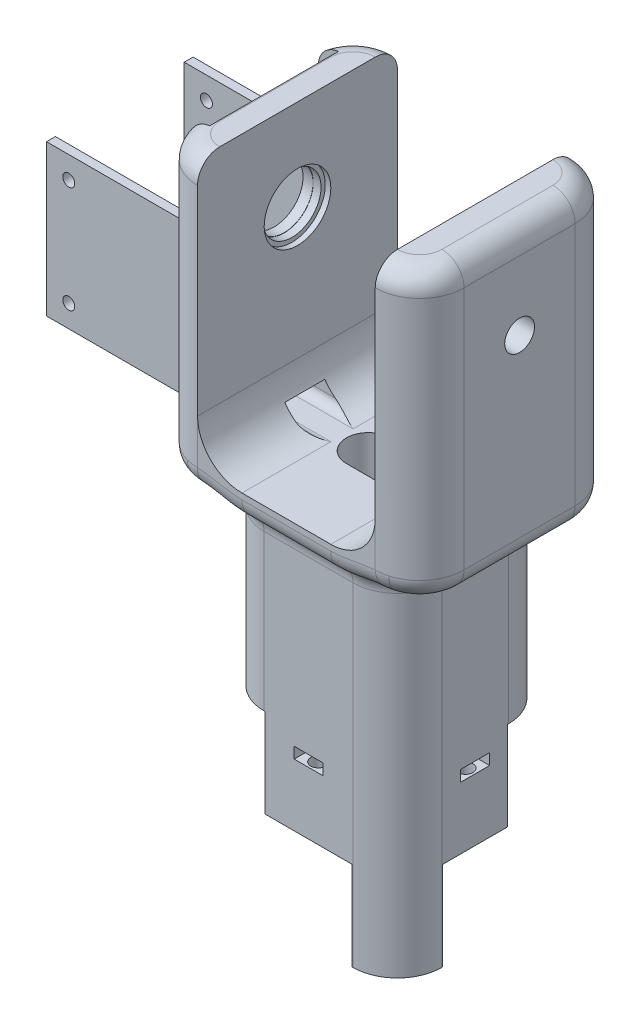
SolidWorks part; units mm, degrees
ref_plane "Plan de face" through (0, 0, 0) normal (0, 0, 1) x (1, 0, 0)
ref_plane "Plan de dessus" through (0, 0, 0) normal (0, 1, 0) x (1, 0, 0)
ref_plane "Plan de droite" through (0, 0, 0) normal (1, 0, 0) x (0, 0, -1)
sketch "Esquisse1" plane through (0, 0, 0) normal (0, 1, 0) x (1, 0, 0)
  line L1 (-20, -17.5) -> (20, -17.5)
  line L2 (-20, -17.5) -> (-20, 17.5)
  line L3 (-20, 17.5) -> (20, 17.5)
  line L4 (20, -17.5) -> (20, 17.5)
  line L5 (-20, -17.5) -> (20, 17.5) construction
  line L6 (-20, 17.5) -> (20, -17.5) construction
  point P0 (0, 0)
  dimension "D1" = 40
  dimension "D2" = 35
extrude "Boss.-Extru.1" add sketch "Esquisse1" along normal blind 80
fillet "Congé1" radius 10 4 edges at (-20, 40, 17.5) (-20, 40, -17.5) (20, 40, -17.5) (20, 40, 17.5)
sketch "Esquisse4" plane through (0, 0, 0) normal (0, -1, 0) x (1, 0, 0)
  line L10 (-20, 17.5) -> (9.8, 17.5)
  line L11 (9.8, 17.5) -> (9.8, 7.3)
  line L12 (9.8, 7.3) -> (20, 7.3)
  line L13 (20, 7.5) -> (20, -7.5) construction
  line L14 (20, 7.3) -> (20, -17.5)
  line L15 (20, -17.5) -> (-9.8, -17.5)
  line L16 (-9.8, -17.5) -> (-9.8, -7.3)
  line L17 (-9.8, -7.3) -> (-20, -7.3)
  line L18 (-20, -7.5) -> (-20, 7.5) construction
  line L19 (-20, -7.3) -> (-20, 17.5)
  line L20 (-10, 17.5) -> (10, 17.5) construction
  line L21 (10, -17.5) -> (-10, -17.5) construction
  arc A2 (-20, -7.5) -> (-10, -17.5) centre (-10, -7.5) ccw construction
  arc A3 (20, 7.5) -> (10, 17.5) centre (10, 7.5) ccw construction
  dimension "D1" = 0.2
  dimension "D2" = 0.2
  dimension "D3" = 0.2
  dimension "D4" = 0.2
extrude "Enlèv. mat.-Extru.3" cut sketch "Esquisse4" against normal blind 20
sketch "Esquisse5" plane through (0, 20, 0) normal (0, -1, 0) x (1, 0, 0)
  line L0 (-20, 7.5) -> (-20, -7.3) construction
  line L9 (-9.8, 7.3) -> (-20, 7.3)
  line L10 (-9.8, 7.3) -> (-9.8, 17.5)
  line L11 (-9.8, 17.5) -> (-20, 17.5)
  line L12 (-20, 7.3) -> (-20, 17.5)
  line L13 (20, -17.5) -> (9.8, -17.5)
  line L14 (20, -17.5) -> (20, -7.3)
  line L15 (20, -7.3) -> (9.8, -7.3)
  line L16 (9.8, -17.5) -> (9.8, -7.3)
  line L17 (9.8, 17.5) -> (-10, 17.5) construction
  line L18 (20, -7.5) -> (20, 7.3) construction
  line L19 (-9.8, -17.5) -> (10, -17.5) construction
  arc A0 (-10, 17.5) -> (-20, 7.5) centre (-10, 7.5) ccw construction
  arc A1 (10, -17.5) -> (20, -7.5) centre (10, -7.5) ccw construction
  dimension "D1" = 0.2
  dimension "D2" = 0.2
  dimension "D3" = 0.2
  dimension "D4" = 0.2
extrude "Enlèv. mat.-Extru.4" cut sketch "Esquisse5" against normal blind 20
sketch "Esquisse6" plane through (0, 80, 0) normal (0, 1, 0) x (1, 0, 0)
  line L1 (-30, -22.5) -> (30, -22.5)
  line L2 (-30, -22.5) -> (-30, 22.5)
  line L3 (-30, 22.5) -> (30, 22.5)
  line L4 (30, -22.5) -> (30, 22.5)
  line L5 (-30, -22.5) -> (30, 22.5) construction
  line L6 (-30, 22.5) -> (30, -22.5) construction
  point P0 (0, 0)
  dimension "D1" = 45
  dimension "D2" = 60
extrude "Boss.-Extru.2" add sketch "Esquisse6" along normal blind 65
fillet "Congé2" radius 10 4 edges at (-30, 112.5, -22.5) (-30, 112.5, 22.5) (30, 112.5, -22.5) (30, 112.5, 22.5)
fillet "Congé5" radius 5 8 edges at (-17.0711, 80, -14.5711) (-17.0711, 80, 14.5711) (-20, 80, 0) (0, 80, -17.5) (17.0711, 80, -14.5711) (20, 80, 0) (17.0711, 80, 14.5711) (0, 80, 17.5)
fillet "Congé7" radius 5 8 edges at (27.0711, 145, -19.5711) (30, 145, 0) (27.0711, 145, 19.5711) (0, 145, 22.5) (-27.0711, 145, 19.5711) (-30, 145, 0) (-27.0711, 145, -19.5711) (0, 145, -22.5)
sketch "Esquisse7" plane through (0, 0, 17.5) normal (0, 0, 1) x (1, 0, 0)
  line L0 (-20, 145) -> (20, 145) construction
  line L1 (-20, 145) -> (20, 145)
  line L2 (-20, 145) -> (-20, 85)
  line L3 (-20, 85) -> (20, 85)
  line L4 (20, 145) -> (20, 85)
  line L5 (30, 140) -> (30, 80) construction
  dimension "D1" = 60
  dimension "D2" = 40
  dimension "D3" = 10
extrude "Enlèv. mat.-Extru.5" cut sketch "Esquisse7" against normal through all and the other way through all
fillet "Congé8" radius 10 2 edges at (20, 85, 0) (-20, 85, 0)
sketch "Esquisse8" plane through (-30, 0, 0) normal (-1, 0, 0) x (0, 0, 1)
  line L0 (-22.5, 140) -> (2.5, 140) construction
  line L1 (-14.5, 138) -> (14.5, 138)
  line L2 (-14.5, 138) -> (-14.5, 89.5)
  line L3 (-14.5, 89.5) -> (14.5, 89.5)
  line L4 (14.5, 138) -> (14.5, 89.5)
  line L5 (-22.5, 140) -> (-22.5, 95) construction
  dimension "D1" = 29
  dimension "D2" = 48.5
  dimension "D3" = 2
  dimension "D4" = 8
extrude "Enlèv. mat.-Extru.6" cut sketch "Esquisse8" against normal blind 4.75
sketch "Esquisse9" plane through (-30, 0, 0) normal (-1, 0, 0) x (0, 0, 1)
  line L0 (-14.5, 138) -> (-14.5, 89.5) construction
  line L1 (-16.5, 125.5) -> (-14.5, 125.5)
  line L2 (-16.5, 125.5) -> (-16.5, 91.5)
  line L3 (-16.5, 91.5) -> (-14.5, 91.5)
  line L4 (-14.5, 125.5) -> (-14.5, 91.5)
  line L5 (16.5, 125.5) -> (14.5, 125.5)
  line L6 (16.5, 125.5) -> (16.5, 91.5)
  line L7 (16.5, 91.5) -> (14.5, 91.5)
  line L8 (14.5, 125.5) -> (14.5, 91.5)
  line L9 (14.5, 89.5) -> (14.5, 138) construction
  line L10 (-12.5, 89.5) -> (12.5, 89.5) construction
  dimension "D1" = 34
  dimension "D2" = 34
  dimension "D3" = 2
  dimension "D4" = 2
  dimension "D5" = 2
  dimension "D6" = 2
extrude "Boss.-Extru.3" add sketch "Esquisse9" along normal blind 30 and the other way blind 5
sketch "Esquisse10" plane through (-25.25, 0, 0) normal (-1, 0, 0) x (0, 0, 1)
  line L0 (-14.5, 89.5) -> (14.5, 89.5) construction
  line L1 (14.5, 89.5) -> (14.5, 138) construction
  circle A0 centre (0, 124.5) radius 3.35
  dimension "D1" = 6.7
  dimension "D2" = 35
  dimension "D3" = 14.5
extrude "Enlèv. mat.-Extru.7" cut sketch "Esquisse10" against normal through all
sketch "Esquisse11" plane through (0, 0, 16.5) normal (0, 0, 1) x (1, 0, 0)
  line L0 (-29.1652, 125.5) -> (-60, 125.5) construction
  line L1 (-60, 91.5) -> (-60, 125.5) construction
  circle A0 centre (-55, 120.5) radius 1.35
  circle A1 centre (-55, 96.5) radius 1.35
  dimension "D1" = 2.7
  dimension "D2" = 2.7
  dimension "D3" = 24
  dimension "D4" = 5
  dimension "D5" = 5
extrude "Enlèv. mat.-Extru.8" cut sketch "Esquisse11" against normal through all
sketch "Esquisse12" plane through (-20, 0, 0) normal (1, 0, 0) x (0, 0, -1)
  circle A0 centre (0, 124.5) radius 6.55
  dimension "D1" = 13.1
extrude "Enlèv. mat.-Extru.9" cut sketch "Esquisse12" against normal blind 3
sketch "Esquisse13" plane through (-20, 0, 0) normal (1, 0, 0) x (0, 0, -1)
  circle A0 centre (0, 124.5) radius 7.5
  dimension "D1" = 15
extrude "Enlèv. mat.-Extru.10" cut sketch "Esquisse13" against normal blind 1.25
sketch "Esquisse14" plane through (20, 0, 0) normal (-1, 0, 0) x (0, 0, 1)
  circle A0 centre (0, 124.5) radius 6.55
  dimension "D1" = 13.1
extrude "Enlèv. mat.-Extru.11" cut sketch "Esquisse14" against normal blind 4
sketch "Esquisse15" plane through (20, 0, 0) normal (-1, 0, 0) x (0, 0, 1)
  circle A0 centre (0, 124.5) radius 7.5
  dimension "D1" = 15
extrude "Enlèv. mat.-Extru.12" cut sketch "Esquisse15" against normal blind 1.25
sketch "Esquisse16" plane through (0, 85, 0) normal (0, 1, 0) x (1, 0, 0)
  line L0 (-4, 0) -> (4, 0) construction
  line L1 (-4, 5) -> (4, 5)
  line L2 (-4, -5) -> (4, -5)
  arc A0 (-4, 5) -> (-4, -5) centre (-4, 0) ccw
  arc A1 (4, -5) -> (4, 5) centre (4, 0) ccw
  point P2 (0, 0)
  dimension "D2" = 5
  dimension "D1" = 8
extrude "Enlèv. mat.-Extru.13" cut sketch "Esquisse16" against normal through all and the other way through all
sketch "Esquisse17" plane through (-30, 0, 0) normal (-1, 0, 0) x (0, 0, 1)
  line L0 (-2.5, 87) -> (2.5, 87) construction
  line L1 (-2.5, 89) -> (2.5, 89)
  line L2 (-2.5, 85) -> (2.5, 85)
  line L5 (22.5, 95) -> (22.5, 80) construction
  line L6 (-14.5, 89.5) -> (14.5, 89.5) construction
  arc A0 (-2.5, 89) -> (-2.5, 85) centre (-2.5, 87) ccw
  arc A1 (2.5, 85) -> (2.5, 89) centre (2.5, 87) ccw
  point P2 (0, 87)
  dimension "D2" = 2
  dimension "D1" = 5
  dimension "D3" = 22.5
  dimension "D4" = 0.5
extrude "Enlèv. mat.-Extru.14" cut sketch "Esquisse17" against normal blind 20
fillet "Congé9" radius 5 12 edges at (0, 80, -22.5) (-27.0711, 80, -19.5711) (-30, 80, 0) (-27.0711, 80, 19.5711) (-15, 80, 22.5) (-15, 80, -22.5) (15, 80, 22.5) (27.0711, 80, 19.5711) (30, 80, 0) (27.0711, 80, -19.5711) (15, 80, -22.5) (0, 80, 22.5)
sketch "Esquisse18" plane through (-30, 0, 0) normal (-1, 0, 0) x (0, 0, 1)
  line L0 (-4.5, 87) -> (-4.5, 89.5)
  line L1 (-14.5, 89.5) -> (14.5, 89.5) construction
  line L2 (-4.5, 89.5) -> (4.5, 89.5)
  line L3 (4.5, 89.5) -> (4.5, 87)
  line L4 (4.5, 87) -> (-4.5, 87)
  arc A0 (-2.5, 89) -> (-2.5, 85) centre (-2.5, 87) ccw construction
  arc A1 (2.5, 85) -> (2.5, 89) centre (2.5, 87) ccw construction
extrude "Enlèv. mat.-Extru.15" cut sketch "Esquisse18" against normal blind 20
sketch "Esquisse19" plane through (0, 20, 0) normal (0, -1, 0) x (-1, 0, 0)
  line L0 (9.8, 17.5) -> (-9.8, 17.5) construction
  circle A0 centre (0, 15.3) radius 1.7
  dimension "D1" = 3.4
  dimension "D2" = 2.2
extrude "Enlèv. mat.-Extru.16" cut sketch "Esquisse19" against normal blind 20
sketch "Esquisse20" plane through (0, 0, -17.5) normal (0, 0, -1) x (-1, 0, 0)
  line L0 (9.8, 20) -> (-9.8, 20) construction
  line L1 (-3.25, 36.5) -> (3.25, 36.5)
  line L2 (-3.25, 36.5) -> (-3.25, 34)
  line L3 (-3.25, 34) -> (3.25, 34)
  line L4 (3.25, 36.5) -> (3.25, 34)
  line L5 (-3.25, 36.5) -> (3.25, 34) construction
  line L6 (-3.25, 34) -> (3.25, 36.5) construction
  point P0 (0, 35.25)
  dimension "D1" = 14
  dimension "D2" = 6.5
  dimension "D3" = 2.5
extrude "Enlèv. mat.-Extru.17" cut sketch "Esquisse20" against normal blind 5.8
sketch "Esquisse21" plane through (0, 20, 0) normal (0, -1, 0) x (1, 0, 0)
  line L0 (-20, 7.3) -> (-20, -7.3) construction
  circle A0 centre (-17.8, 0) radius 1.7
  dimension "D1" = 3.4
  dimension "D2" = 2.2
extrude "Enlèv. mat.-Extru.18" cut sketch "Esquisse21" against normal blind 20
sketch "Esquisse22" plane through (-20, 0, 0) normal (-1, 0, 0) x (0, 0, 1)
  line L0 (7.3, 20) -> (-7.3, 20) construction
  line L1 (-3.25, 36.5) -> (3.25, 36.5)
  line L2 (-3.25, 36.5) -> (-3.25, 34)
  line L3 (-3.25, 34) -> (3.25, 34)
  line L4 (3.25, 36.5) -> (3.25, 34)
  line L5 (-3.25, 36.5) -> (3.25, 34) construction
  line L6 (-3.25, 34) -> (3.25, 36.5) construction
  point P0 (0, 35.25)
  dimension "D1" = 6.5
  dimension "D2" = 2.5
  dimension "D3" = 14
extrude "Enlèv. mat.-Extru.19" cut sketch "Esquisse22" against normal blind 5.8
mirror "Symétrie1" about plane through (0, 0, 0) normal (0, 0, 1) of "Enlèv. mat.-Extru.17", "Enlèv. mat.-Extru.16"
mirror "Symétrie2" about plane through (0, 0, 0) normal (1, 0, 0) of "Enlèv. mat.-Extru.19", "Enlèv. mat.-Extru.18"
sketch "Esquisse23" plane through (0, 138, 0) normal (0, -1, 0) x (1, 0, 0)
  line L0 (-29.798, -14.5) -> (-60, -14.5) construction
  line L1 (-25.25, 14.5) -> (-30, 14.5)
  line L2 (-25.25, 14.5) -> (-25.25, -14.5)
  line L3 (-25.25, -14.5) -> (-30, -14.5)
  line L4 (-30, 14.5) -> (-30, -14.5)
  line L5 (-30, 12.5) -> (-30, -12.5) construction
extrude "Enlèv. mat.-Extru.20" cut sketch "Esquisse23" against normal blind 10
hole_wizard "Dégagement M22" positions "Esquisse24" profile "Esquisse25" size "M2" standard "Ansi Metric" slot yes
sketch "Esquisse24" plane through (-25.25, 0, 0) normal (-1, 0, 0) x (0, 0, 1)
  point P0 (0, 124.5)
sketch "Esquisse25" plane through (-25.25, 124.5, 0) normal (0, 1, 0) x (0, 0, 1)
  line L0 (0, 0) -> (0, 13.9056)
  line L1 (0, 13.9056) -> (6.5, 10)
  line L2 (6.5, 10) -> (6.5, 0)
  line L5 (6.5, 0) -> (0, 0)
  line L10 (0, 13.9056) -> (-6.5, 10) construction
  line L11 (0, -6.35) -> (0, 107.95) construction
  dimension "Diamètre du perçage" = 13
  dimension "Profondeur du perçage" = 10
  dimension "Angle de pointe" = 118
equation "\"1.25.00mm\"=4"
